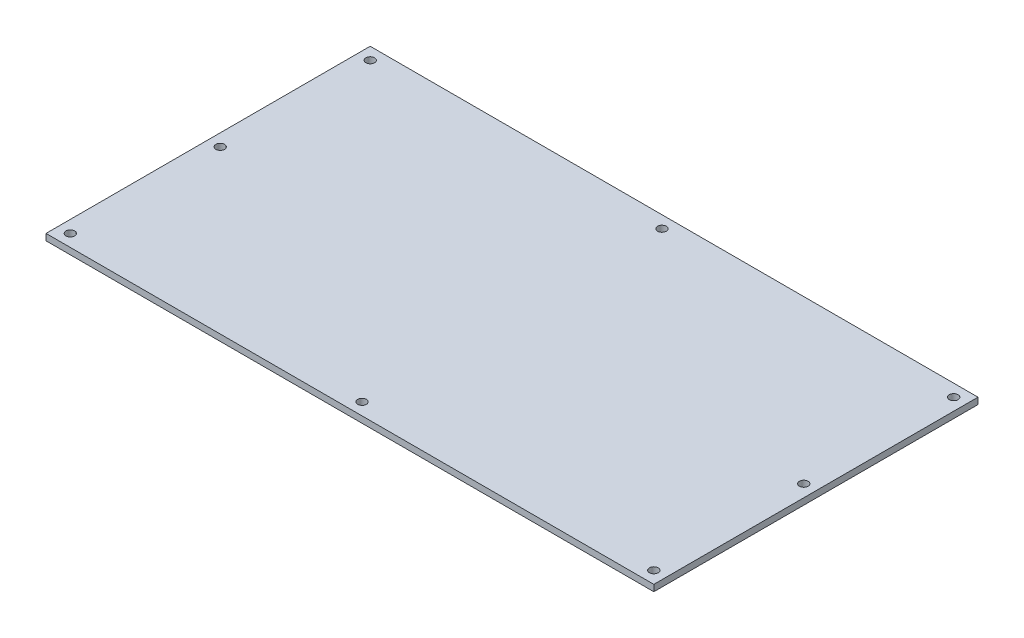
SolidWorks part; units mm, degrees
ref_plane "Front Plane" through (0, 0, 0) normal (0, 0, 1) x (1, 0, 0)
ref_plane "Top Plane" through (0, 0, 0) normal (0, 1, 0) x (1, 0, 0)
ref_plane "Right Plane" through (0, 0, 0) normal (1, 0, 0) x (0, 0, -1)
sketch "Sketch1" plane through (0, 0, 0) normal (0, 1, 0) x (1, 0, 0)
  line L0 (150, 160) -> (150, 0) construction
  line L1 (0, 0) -> (300, 0)
  line L2 (0, 0) -> (0, 160)
  line L3 (0, 160) -> (300, 160)
  line L4 (300, 0) -> (300, 160)
  line L5 (0, 80) -> (300, 80) construction
  line L6 (170, 160) -> (170, 0) construction
  circle A0 centre (294, 6) radius 2.15
  circle A1 centre (6, 6) radius 2.15
  circle A2 centre (294, 154) radius 2.15
  circle A3 centre (6, 154) radius 2.15
  circle A4 centre (294, 80) radius 2.15
  circle A5 centre (150, 6) radius 2.15
  circle A6 centre (150, 154) radius 2.15
  circle A7 centre (6, 80) radius 2.15
  dimension "D4" = 4.3
  dimension "D7" = 4.3
  dimension "D9" = 4.3
  dimension "D1" = 300
  dimension "D2" = 160
  dimension "D3" = 170
  dimension "D5" = 6
  dimension "D6" = 6
  dimension "D8" = 6
  dimension "D10" = 6
extrude "Boss-Extrude1" add sketch "Sketch1" along normal blind 3.175
